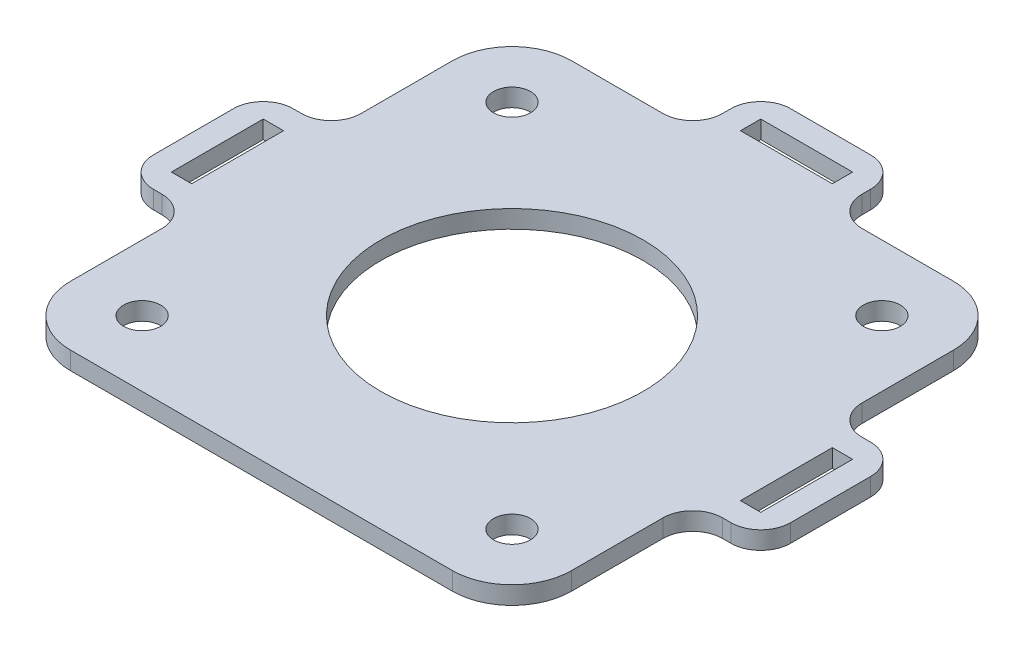
SolidWorks part; units mm, degrees
material "AISI 304"
ref_plane "Front Plane" through (0, 0, 0) normal (0, 0, 1) x (1, 0, 0)
ref_plane "Top Plane" through (0, 0, 0) normal (0, 1, 0) x (1, 0, 0)
ref_plane "Right Plane" through (0, 0, 0) normal (1, 0, 0) x (0, 0, -1)
sketch "Sketch1" plane through (0, 0, 0) normal (0, 1, 0) x (1, 0, 0)
  line L0 (0, 0) -> (0, 33.6449) construction
  line L5 (0, 0) -> (35.5051, 0) construction
  line L40 (23, 3.85) -> (24.7, 3.85)
  line L41 (23, 3.85) -> (23, -3.85)
  line L62 (23, -3.85) -> (24.7, -3.85)
  line L63 (24.7, 3.85) -> (24.7, -3.85)
  line L64 (23, 3.85) -> (24.7, -3.85) construction
  line L65 (23, -3.85) -> (24.7, 3.85) construction
  line L66 (21, 5.85) -> (26.7, 5.85)
  line L68 (21, -5.85) -> (26.7, -5.85)
  line L69 (26.7, 5.85) -> (26.7, -5.85)
  line L70 (21, 21) -> (5.85, 21)
  line L71 (21, 21) -> (21, 5.85)
  line L72 (21, -21) -> (5.85, -21)
  line L73 (-21, 21) -> (-21, 5.85)
  line L74 (21, 21) -> (-21, -21) construction
  line L75 (21, -21) -> (-21, 21) construction
  line L80 (-5.85, -21) -> (5.85, -21)
  line L84 (-23, -3.85) -> (-24.7, -3.85)
  line L85 (-23, -3.85) -> (-23, 3.85)
  line L86 (-23, 3.85) -> (-24.7, 3.85)
  line L87 (-24.7, -3.85) -> (-24.7, 3.85)
  line L88 (-26.7, -5.85) -> (-26.7, 5.85)
  line L89 (-23, -3.85) -> (-24.7, 3.85) construction
  line L90 (-23, 3.85) -> (-24.7, -3.85) construction
  line L91 (-21, -5.85) -> (-26.7, -5.85)
  line L92 (-21, 5.85) -> (-26.7, 5.85)
  line L93 (-3.85, 23) -> (-3.85, 24.7)
  line L94 (-3.85, 23) -> (3.85, 23)
  line L95 (3.85, 23) -> (3.85, 24.7)
  line L96 (-3.85, 24.7) -> (3.85, 24.7)
  line L97 (-5.85, 26.7) -> (5.85, 26.7)
  line L98 (-3.85, 23) -> (3.85, 24.7) construction
  line L99 (3.85, 23) -> (-3.85, 24.7) construction
  line L100 (-5.85, 21) -> (-5.85, 26.7)
  line L101 (5.85, 21) -> (5.85, 26.7)
  line L102 (-5.85, -21) -> (-21, -21)
  line L103 (-5.85, 21) -> (-21, 21)
  line L104 (-21, -5.85) -> (-21, -21)
  line L105 (21, -5.85) -> (21, -21)
  line L106 (3.85, -23) -> (3.85, -24.7) [skipped]
  line L107 (3.85, -24.7) -> (-3.85, -24.7) [skipped]
  line L108 (-3.85, -23) -> (-3.85, -24.7) [skipped]
  line L109 (3.85, -23) -> (-3.85, -23) [skipped]
  line L110 (3.85, -23) -> (-3.85, -24.7) construction
  line L111 (-3.85, -23) -> (3.85, -24.7) construction
  line L112 (-5.85, -21) -> (-5.85, -26.7) [skipped]
  line L113 (5.85, -21) -> (5.85, -26.7) [skipped]
  line L114 (5.85, -26.7) -> (-5.85, -26.7) [skipped]
  circle A1 centre (-15.5, 15.5) radius 1.55
  circle A2 centre (15.5, 15.5) radius 1.55
  circle A3 centre (15.5, -15.5) radius 1.55
  circle A4 centre (-15.5, -15.5) radius 1.55
  circle A5 centre (0, 0) radius 11
  point P0 (0, 0)
  point P3 (23.85, 0)
  point P24 (0, -23.85)
  point P37 (-23.85, 0)
  point P46 (0, 23.85)
  point P55 (0, 0)
  point P66 (0, 0)
  point P84 (0, 0)
  dimension "D1" = 42
  dimension "D2" = 3.1
  dimension "D8" = 2
  dimension "D15" = 22
  dimension "D9" = 15.5
  dimension "D3" = 2
  dimension "D4" = 2
  dimension "D5" = 42
  dimension "D10" = 2
  dimension "D11" = 1.7
  dimension "D12" = 7.7
  dimension "D13" = 4
  dimension "D14" = 15.5
  dimension "D6" = 2
  dimension "D7" = 2
extrude "Boss-Extrude1" add sketch "Sketch1" along normal blind 1.5
fillet "Fillet2" radius 5 4 edges at (21, 0.75, 21) (-21, 0.75, 21) (-21, 0.75, -21) (21, 0.75, -21)
fillet "Fillet1" radius 2.5 12 edges at (-21, 0.75, -5.85) (-26.7, 0.75, -5.85) (-21, 0.75, 5.85) (-26.7, 0.75, 5.85) (5.85, 0.75, -21) (5.85, 0.75, -26.7) (-5.85, 0.75, -26.7) (-5.85, 0.75, -21) (21, 0.75, 5.85) (26.7, 0.75, 5.85) (26.7, 0.75, -5.85) (21, 0.75, -5.85)
